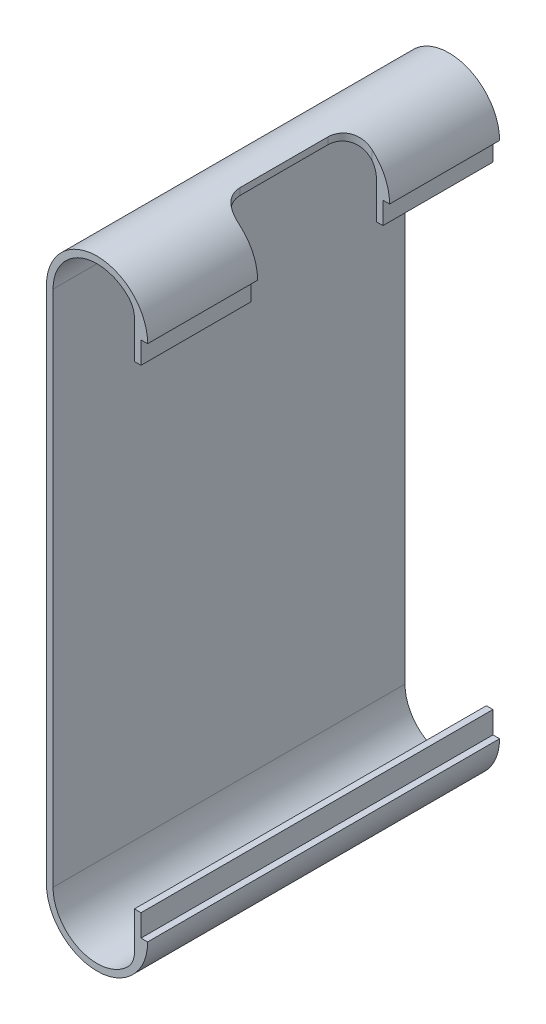
SolidWorks part; units mm, degrees
ref_plane "Front Plane" through (0, 0, 0) normal (0, 0, 1) x (1, 0, 0)
ref_plane "Top Plane" through (0, 0, 0) normal (0, 1, 0) x (1, 0, 0)
ref_plane "Right Plane" through (0, 0, 0) normal (1, 0, 0) x (0, 0, -1)
sketch "Sketch1" plane through (0, 0, 0) normal (0, 0, 1) x (1, 0, 0)
  line L0 (0, -75) -> (-40, -75) construction
  line L1 (33, 42.75) -> (-40, 42.75) construction
  line L3 (-40, -75) -> (-40, 160.5)
  line L4 (-43, -75) -> (-43, 160.5)
  line L5 (0, 160.5) -> (3, 160.5)
  line L6 (0, -75) -> (3, -75)
  arc A0 (-40, -75) -> (0, -75) centre (-20, -75) ccw
  arc A1 (-40, 160.5) -> (0, 160.5) centre (-20, 160.5) cw
  arc A2 (-43, 160.5) -> (3, 160.5) centre (-20, 160.5) cw
  arc A3 (-43, -75) -> (3, -75) centre (-20, -75) ccw
  dimension "D1" = 3
extrude "Boss-Extrude1" add sketch "Sketch1" against normal up to surface (160 mm away)
ref_plane "Plane1" through (3, 0, 0) normal (1, 0, 0) x (0, 0, -1)
sketch "Sketch2" plane through (3, 0, 0) normal (1, 0, 0) x (0, 0, -1)
  line L6 (193.5, 42.75) -> (-33.0117, 42.75) construction
  line L7 (193.5, 16.75) -> (193.5, 68.75) construction
  line L8 (110, 157.25) -> (110, 185.25)
  line L9 (50, 185.25) -> (110, 185.25)
  line L10 (50, 157.25) -> (50, 185.25)
  line L11 (50, 157.25) -> (110, 157.25)
extrude "Cut-Extrude1" cut sketch "Sketch2" against normal blind 18
fillet "Fillet1" radius 10 2 edges at (-15, 181.4074, -50) (-15, 181.4074, -110)
sketch "Sketch3" plane through (0, 0, -160) normal (0, 0, -1) x (-1, 0, 0)
  line L1 (0, 171.8578) -> (3, 171.8578)
  line L2 (0, 171.8578) -> (0, 150.5)
  line L3 (0, 150.5) -> (3, 150.5)
  line L4 (3, 171.8578) -> (3, 150.5)
  arc A0 (43, 160.5) -> (-3, 160.5) centre (20, 160.5) ccw construction
  point P4 (0.2013, 172.2053)
extrude "Boss-Extrude2" add sketch "Sketch3" against normal up to surface (50 mm away) up to face at (-0.9718, 168.4987, -110)
sketch "Sketch4" plane through (0, 0, 0) normal (0, 0, 1) x (1, 0, 0)
  line L4 (0, 171.8578) -> (-3, 171.8578)
  line L5 (-3, 171.8578) -> (-3, 150.5)
  line L6 (-3, 150.5) -> (0, 150.5)
  line L7 (0, 150.5) -> (0, 171.8578)
  line L8 (0, 171.8578) -> (-3, 171.8578)
  line L9 (-3, 171.8578) -> (-3, 150.5)
  line L10 (-3, 150.5) -> (0, 150.5)
  line L11 (0, 150.5) -> (0, 171.8578)
  dimension "D1" = 0
extrude "Boss-Extrude3" add sketch "Sketch4" against normal up to surface (50 mm away) up to face at (-0.9718, 168.4987, -50)
sketch "Sketch5" plane through (0, 0, -160) normal (0, 0, -1) x (-1, 0, 0)
  line L1 (3, -65) -> (0, -65)
  line L2 (3, -65) -> (3, -86.3578)
  line L3 (3, -86.3578) -> (0, -86.3578)
  line L4 (0, -65) -> (0, -86.3578)
  arc A0 (-3, -75) -> (43, -75) centre (20, -75) ccw construction
  point P4 (-0.3775, -85.6657)
  dimension "D1" = 3
extrude "Boss-Extrude4" add sketch "Sketch5" against normal up to surface (160 mm away) up to face at (-15.4525, 73.4548, 0)
fillet "Fillet2" radius 10 3 edges at (-3, 171.0357, -25) (-3, 171.0357, -135) (-3, -85.5357, -80)
